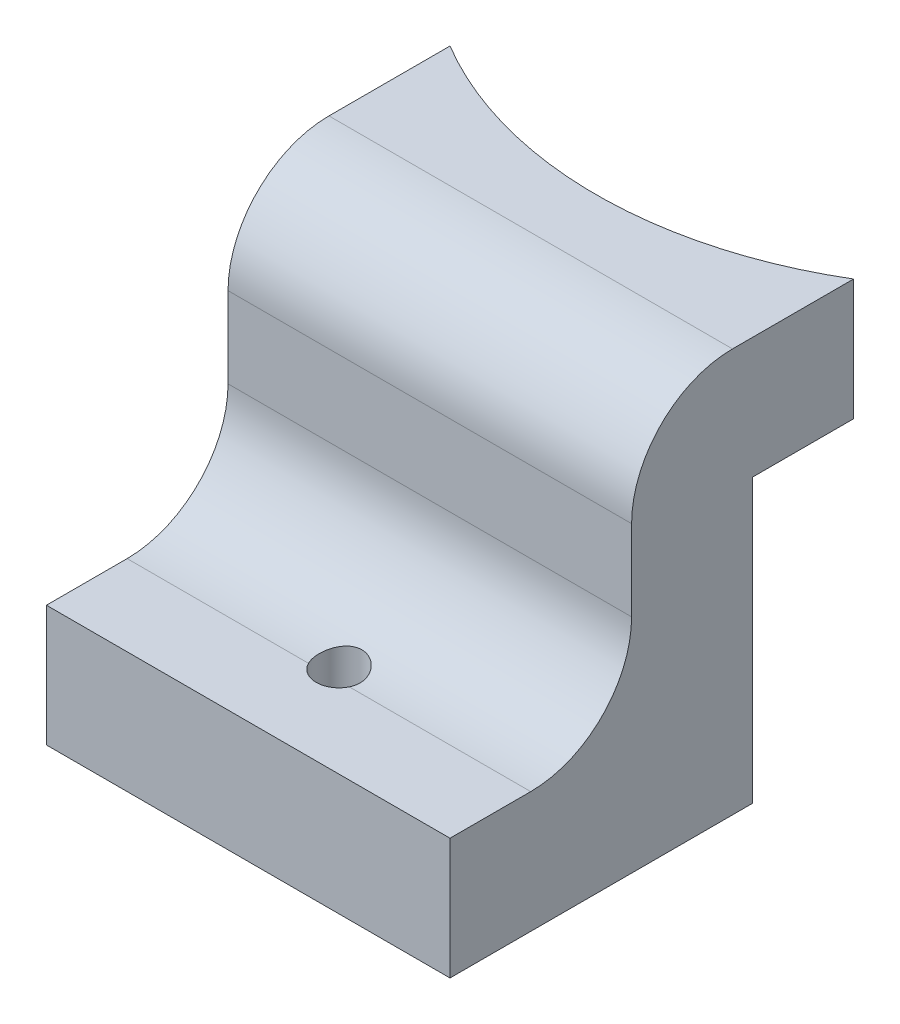
SolidWorks part; units mm, degrees
material "6061 Alloy"
ref_plane "Front Plane" through (0, 0, 0) normal (0, 0, 1) x (1, 0, 0)
ref_plane "Top Plane" through (0, 0, 0) normal (0, 1, 0) x (1, 0, 0)
ref_plane "Right Plane" through (0, 0, 0) normal (1, 0, 0) x (0, 0, -1)
sketch "Sketch1" plane through (0, 0, 0) normal (0, 1, 0) x (1, 0, 0)
  line L0 (10, 5) -> (-10, -5) construction
  line L1 (-10, 5) -> (10, 5)
  line L2 (-10, 5) -> (-10, -5)
  line L3 (-10, -5) -> (10, -5)
  line L4 (10, 5) -> (10, -5)
  line L5 (-10, 5) -> (10, -5) construction
  point P2 (0, 0)
  dimension "D1" = 20
  dimension "D2" = 10
extrude "Boss-Extrude1" add sketch "Sketch1" along normal blind 6
sketch "Sketch2" plane through (0, 6, 0) normal (0, 1, 0) x (1, 0, 0)
  circle A0 centre (0, 21.7407) radius 19.5
  dimension "D1" = 39
extrude "Cut-Extrude1" cut sketch "Sketch2" against normal blind 9
sketch "Sketch3" plane through (0, 6, 0) normal (0, 1, 0) x (1, 0, 0)
  line L0 (-10, 5) -> (-10, -5) construction
  line L1 (-10, 0) -> (10, 0)
  line L2 (-10, 0) -> (-10, -6)
  line L3 (-10, -6) -> (10, -6)
  line L4 (10, 0) -> (10, -6)
  line L5 (-10, -5) -> (10, -5) construction
  line L6 (10, -5) -> (10, 5) construction
  dimension "D1" = 5
  dimension "D2" = 0
  dimension "D3" = 20
  dimension "D4" = 6
extrude "Boss-Extrude2" add sketch "Sketch3" against normal blind 20
sketch "Sketch4" plane through (0, 0, 6) normal (0, 0, 1) x (1, 0, 0)
  line L0 (-10, -14) -> (10, -14) construction
  line L1 (-10, -8) -> (10, -8)
  line L2 (-10, -8) -> (-10, -14)
  line L3 (-10, -14) -> (10, -14)
  line L4 (10, -8) -> (10, -14)
  line L6 (-10, -14) -> (-10, 6) construction
  dimension "D1" = 6
  dimension "D2" = 20
  dimension "D3" = 0
extrude "Boss-Extrude3" add sketch "Sketch4" along normal blind 9
sketch "Sketch9" plane through (0, -14, 0) normal (0, -1, 0) x (1, 0, 0)
  line L0 (0, 15) -> (0, 0) construction
  line L1 (-10, 15) -> (10, 15) construction
  line L2 (10, 0) -> (-10, 0) construction
  line L3 (-10, 10.5) -> (10, 10.5) construction
  line L4 (-10, 0) -> (-10, 15) construction
  line L5 (10, 15) -> (10, 0) construction
  point P12 (0, 10.5)
  dimension "D1" = 4.5
hole_wizard "#4-40 Tapped Hole2" positions "Sketch10" profile "Sketch11" tap size "#4-40" standard "ANSI Inch"
sketch "Sketch10" plane through (0, -14, 0) normal (0, -1, 0) x (-1, 0, 0)
  point P0 (0, -10.5)
sketch "Sketch11" plane through (0, -14, 10.5) normal (1, 0, 0) x (0, 0, -1)
  line L0 (0, 0) -> (0, 8.2792)
  line L1 (0, 8.2792) -> (1.1303, 7.6)
  line L2 (1.1303, 7.6) -> (1.1303, 0)
  line L5 (1.1303, 0) -> (0, 0)
  line L10 (0, 8.2792) -> (-1.1303, 7.6) construction
  line L11 (0, -6.35) -> (0, 107.95) construction
  dimension "Tap Drill Dia." = 2.2606
  dimension "Tap Drill Depth" = 7.6
  dimension "Drill Angle" = 118
cosmetic thread "Hole Thread2" parameters "D1"=5.69, "D2"=2.8448
fillet "Fillet2" radius 5 2 edges at (0, 6, 6) (0, -8, 6)
